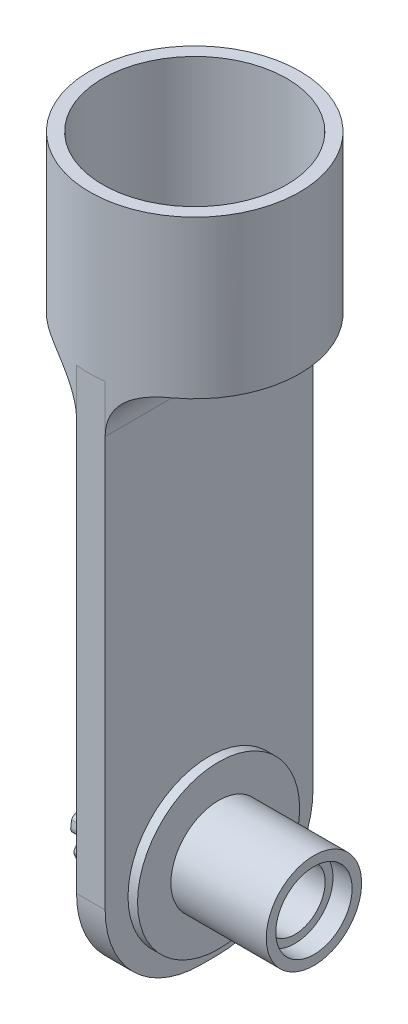
SolidWorks part; units mm, degrees
material "7075-T6 (SN)"
ref_plane "Front Plane" through (0, 0, 0) normal (0, 0, 1) x (1, 0, 0)
ref_plane "Top Plane" through (0, 0, 0) normal (0, 1, 0) x (1, 0, 0)
ref_plane "Right Plane" through (0, 0, 0) normal (1, 0, 0) x (0, 0, -1)
sketch "Sketch2" plane through (0, 0, 0) normal (0, 1, 0) x (-1, 0, 0)
  circle A0 centre (0, 0) radius 11
  dimension "D1" = 22
extrude "Boss-Extrude2" add sketch "Sketch2" against normal blind 1.5
sketch "Sketch3" plane through (0, 0, 0) normal (0, -1, 0) x (-1, 0, 0)
  circle A0 centre (0, 0) radius 9.652
  circle A1 centre (0, 0) radius 11
  circle A3 centre (0, 0) radius 11 construction
  dimension "D2" = 19.304
extrude "Boss-Extrude3" add sketch "Sketch3" against normal blind 15
sketch "Sketch4" plane through (0, -1.5, 0) normal (0, -1, 0) x (1, 0, 0)
  line L1 (-1.5, 10.8972) -> (1.5, 10.8972)
  line L2 (-1.5, 10.8972) -> (-1.5, -10.8972)
  line L3 (-1.5, -10.8972) -> (1.5, -10.8972)
  line L4 (1.5, 10.8972) -> (1.5, -10.8972)
  line L5 (-1.5, 10.8972) -> (1.5, -10.8972) construction
  line L6 (-1.5, -10.8972) -> (1.5, 10.8972) construction
  circle A0 centre (0, 0) radius 11 construction
  arc A1 (1.5, 10.8972) -> (-1.5, 10.8972) centre (0, 0) ccw construction
  arc A2 (-1.5, -10.8972) -> (1.5, -10.8972) centre (0, 0) ccw construction
  point P0 (0, 0)
  dimension "D1" = 3
extrude "Boss-Extrude4" add sketch "Sketch4" along normal blind 58
sketch "Sketch7" plane through (1.5, 0, 0) normal (1, 0, 0) x (0, 0, -1)
  line L0 (10.8972, -59.5) -> (-10.8972, -59.5) construction
  line L1 (0, -49.5) -> (0, -59.5) construction
  circle A0 centre (0, -49.5) radius 11.5 construction
  circle A2 centre (0, -38) radius 2.1
  circle A3 centre (11.5, -49.5) radius 2.1
  circle A4 centre (0, -61) radius 2.1
  circle A5 centre (-11.5, -49.5) radius 2.1
  dimension "D1" = 23
  dimension "D2" = 4.2
  dimension "D3" = 10
extrude "Cut-Extrude2" [suppressed] cut sketch "Sketch7" against normal up to surface (3 mm away)
ref_plane "Plane1" through (0, 0, 0) normal (-1, 0, 0) x (0, 0, 1)
sketch "Sketch11" plane through (1.5, 0, 0) normal (1, 0, 0) x (0, 0, -1)
  line L0 (10.8972, -59.5) -> (-10.8972, -59.5) construction
  circle A0 centre (0, -49.5) radius 8.5
  dimension "D1" = 17
  dimension "D2" = 10
extrude "Boss-Extrude11" add sketch "Sketch11" along normal blind 1 contours A0
sketch "Sketch8" plane through (2.5, 0, 0) normal (-1, 0, 0) x (0, 0, 1)
  circle A0 centre (0, -49.5) radius 5
  circle A1 centre (0, -49.5) radius 8.5 construction
  dimension "D1" = 10
extrude "Boss-Extrude6" add sketch "Sketch8" against normal blind 10 contours A0
sketch "Sketch17" plane through (-1.5, 0, 0) normal (-1, 0, 0) x (0, 0, 1)
  circle A1 centre (0, -49.5) radius 8.5
  circle A2 centre (0, -49.5) radius 5 construction
  dimension "D1" = 17
extrude "Boss-Extrude9" add sketch "Sketch17" along normal blind 1
sketch "Sketch19" plane through (-2.5, 0, 0) normal (-1, 0, 0) x (0, 0, 1)
  circle A0 centre (0, -49.5) radius 5.775
  dimension "D1" = 11.55
extrude "Boss-Extrude10" add sketch "Sketch19" along normal blind 4.75 contours A0
sketch "Sketch16" plane through (-1.5, 0, 0) normal (-1, 0, 0) x (0, 0, 1)
  line L0 (-10.8972, -1.5) -> (10.8972, -1.5) construction
  line L1 (-9.8972, -5.5) -> (9.8972, -5.5) construction
  line L2 (-9.8972, -5.5) -> (-9.8972, -46.1172) construction
  line L3 (-9.8972, -46.1172) -> (9.8972, -46.1172) construction
  line L4 (9.8972, -5.5) -> (9.8972, -46.1172) construction
  line L7 (0, -5.5) -> (0, -46.1172) construction
  line L8 (-9.8972, -25.8086) -> (9.8972, -25.8086) construction
  line L9 (-7.2829, -6.5) -> (7.2829, -6.5)
  line L10 (7.2829, -6.5) -> (0, -24.8086)
  line L11 (0, -24.8086) -> (-7.2829, -6.5)
  line L12 (-8.8972, -6.5) -> (-1.2165, -25.8086)
  line L13 (-1.2165, -25.8086) -> (-8.8972, -45.1172)
  line L14 (-8.8972, -45.1172) -> (-8.8972, -6.5)
  line L16 (8.8972, -6.5) -> (1.2165, -25.8086)
  line L17 (1.2165, -25.8086) -> (8.8972, -45.1172)
  line L18 (8.8972, -45.1172) -> (8.8972, -6.5)
  line L19 (-7.2829, -45.1172) -> (7.2829, -45.1172) construction
  line L20 (7.2829, -45.1172) -> (0, -26.8086)
  line L21 (0, -26.8086) -> (-7.2829, -45.1172)
  line L22 (0, -5.5) -> (0, -1.5) construction
  line L23 (10.8972, -59.5) -> (10.8972, -1.5) construction
  line L24 (-10.8972, -59.5) -> (-10.8972, -1.5) construction
  arc A0 (7.2829, -45.1172) -> (-7.2829, -45.1172) centre (0, -49.5) ccw
  circle A1 centre (0, -49.5) radius 5.775 construction
  circle A2 centre (0, -49.5) radius 8.5 construction
  circle A3 centre (0, -49.5) radius 5 construction
  circle A5 centre (0, -49.5) radius 5 construction
  dimension "D4" = 1
  dimension "D1" = 1
  dimension "D2" = 4
  dimension "D3" = 1.5
  dimension "D5" = 1
  dimension "D6" = 1
  dimension "D7" = 1
extrude "Cut-Extrude4" [suppressed] cut sketch "Sketch16" against normal up to surface (3 mm away)
sketch "Sketch14" plane through (-2.5, 0, 0) normal (-1, 0, 0) x (0, 0, 1)
  line L0 (-0.25, -44.5392) -> (0.25, -44.5392) construction
  line L1 (-0.25, -44.5392) -> (-1, -43.8122)
  line L2 (0.25, -44.5392) -> (1, -43.8122)
  line L3 (0, -44.5392) -> (0, -44.75) construction
  line L4 (0, -44.75) -> (-0.4187, -44.75) construction
  line L5 (0, -44.5392) -> (0, -43.725) construction
  line L6 (0, -43.725) -> (-0.3248, -43.725) construction
  line L7 (0, -49.5) -> (0, -44.75) construction
  arc A0 (-1, -43.8122) -> (1, -43.8122) centre (0, -49.5) cw
  arc A1 (-0.25, -44.5392) -> (0.25, -44.5392) centre (0, -49.5) cw
  circle A2 centre (0, -49.5) radius 4.75 construction
  circle A3 centre (0, -49.5) radius 5.775 construction
  circle A5 centre (0, -49.5) radius 8.5 construction
  dimension "D1" = 9.5
  dimension "D2" = 11.55
  dimension "D3" = 0.8142
  dimension "D4" = 2
  dimension "D5" = 0.5
extrude "Cut-Extrude5" cut sketch "Sketch14" along normal up to surface (4.75 mm away) up to face at (-7.25, -49.5, 5.775)
fillet "Fillet3" radius 0.5 4 edges at (-4.875, -43.8122, 1) (-4.875, -44.5392, 0.25) (-4.875, -44.5392, -0.25) (-4.875, -43.8122, -1)
pattern_circular "CirPattern2" count 11 over 360 about axis through (-7.25, -49.5, 0) along (1, 0, 0) of "Fillet3", "Cut-Extrude5"
sketch "Sketch15" plane through (12.5, 0, 0) normal (1, 0, 0) x (0, 0, -1)
  circle A0 centre (0, -49.5) radius 3.175
  dimension "D1" = 6.35
extrude "encoder_bed" cut sketch "Sketch15" against normal blind 6
fillet "Fillet4" [suppressed] radius 1
fillet "Fillet5" radius 10 2 edges at (0, -59.5, -10.8972) (0, -59.5, 10.8972)
ref_plane "Plane2" through (0, 0, 0) normal (-1, 0, 0) x (0, 0, 1)
ref_axis "Axis1" through (20.3679, -49.5, 0) along (-1, 0, 0)
sketch "Sketch20" plane through (0, 0, 0) normal (0, 0, 1) x (1, 0, 0)
  line L0 (-10.5, -1.5) -> (-1.5, -1.5)
  line L1 (-1.5, -1.5) -> (-1.5, -15.5)
  line L2 (-1.5, -49.5) -> (-1.5, -1.5) construction
  line L3 (-1.5, -15.5) -> (-10.5, -1.5)
  line L4 (-1.5, -15.5) -> (1.5, -15.5) construction
  line L5 (1.5, -49.5) -> (1.5, -1.5) construction
  line L6 (1.5, -15.5) -> (10.5, -1.5)
  line L7 (10.5, -1.5) -> (1.5, -1.5)
  line L8 (1.5, -1.5) -> (1.5, -15.5)
  dimension "D1" = 14
  dimension "D2" = 9
extrude "Boss-Extrude12" [suppressed] add sketch "Sketch20" along normal mid plane 3
fillet "Fillet6" [suppressed] radius 2
fillet "Fillet7" radius 5 2 edges at (-1.5, -1.5, 0) (1.5, -1.5, 0)
sketch "Sketch21" plane through (12.5, 0, 0) normal (1, 0, 0) x (0, 0, -1)
  circle A0 centre (0, -49.5) radius 4
  dimension "D1" = 8
extrude "Cut-Extrude6" cut sketch "Sketch21" against normal blind 2
